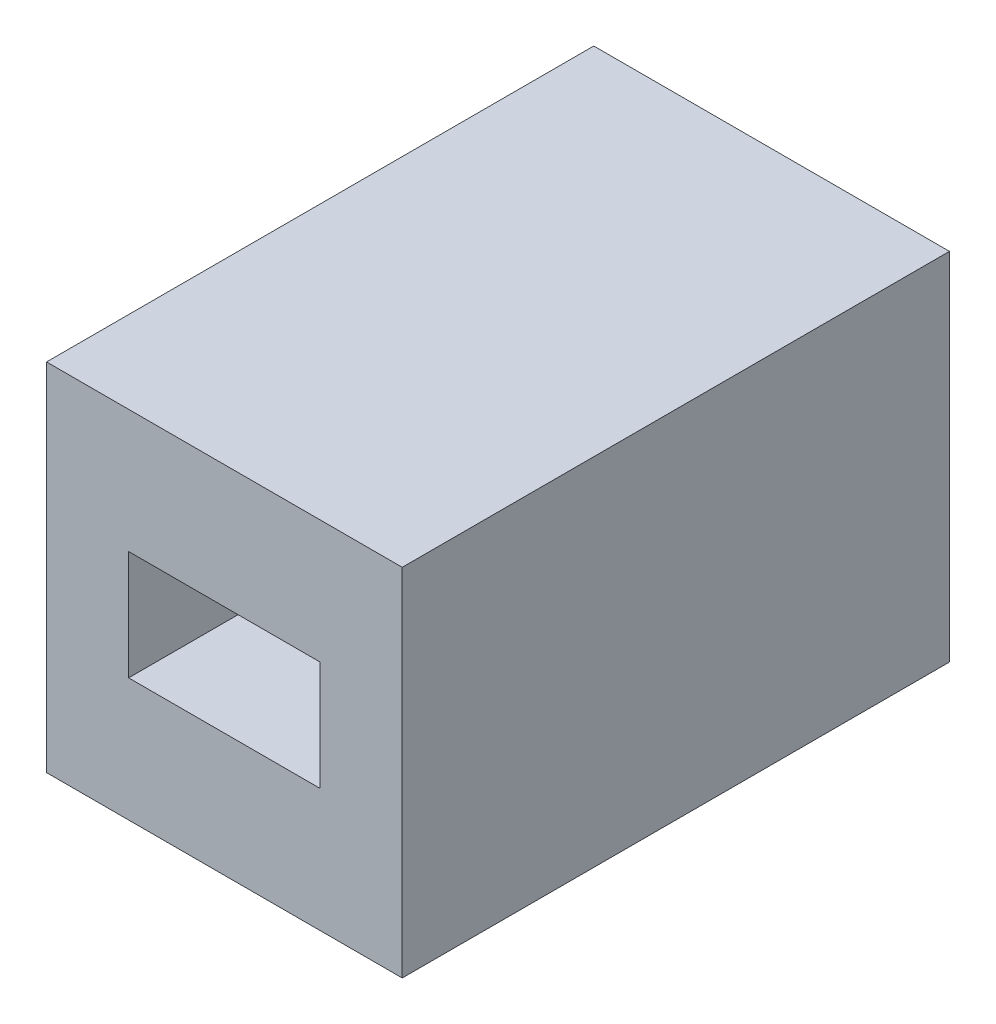
SolidWorks part; units mm, degrees
ref_plane "정면" through (0, 0, 0) normal (0, 0, 1) x (1, 0, 0)
ref_plane "윗면" through (0, 0, 0) normal (0, 1, 0) x (1, 0, 0)
ref_plane "우측면" through (0, 0, 0) normal (1, 0, 0) x (0, 0, -1)
ref_axis "기준축2" through (0, 0, 210) along (0, 0, -1)
ref_axis "기준축4" through (0, 55, 0) along (0, -1, 0)
sketch "스케치1" plane through (0, 0, 0) normal (0, 0, 1) x (1, 0, 0)
  line L1 (-30, 15) -> (30, 15) construction
  line L2 (-30, 15) -> (-30, -15) construction
  line L3 (-30, -15) -> (30, -15) construction
  line L4 (30, 15) -> (30, -15) construction
  line L5 (-65, 65) -> (65, 65)
  line L6 (-65, 65) -> (-65, -65)
  line L7 (-65, -65) -> (65, -65)
  line L8 (65, 65) -> (65, -65)
  line L9 (-35, 20) -> (35, 20)
  line L10 (-35, 20) -> (-35, -20)
  line L11 (-35, -20) -> (35, -20)
  line L12 (35, 20) -> (35, -20)
  point P5 (0, 15)
  point P7 (30, 0)
  point P11 (0, -65)
  point P14 (65, 0)
  dimension "D1" = 60
  dimension "D2" = 30
  dimension "D3" = 130
  dimension "D4" = 130
  dimension "D5" = 5
  dimension "D6" = 5
  dimension "D7" = 5
  dimension "D8" = 5
extrude "보스-돌출1" add sketch "스케치1" along normal blind 200
